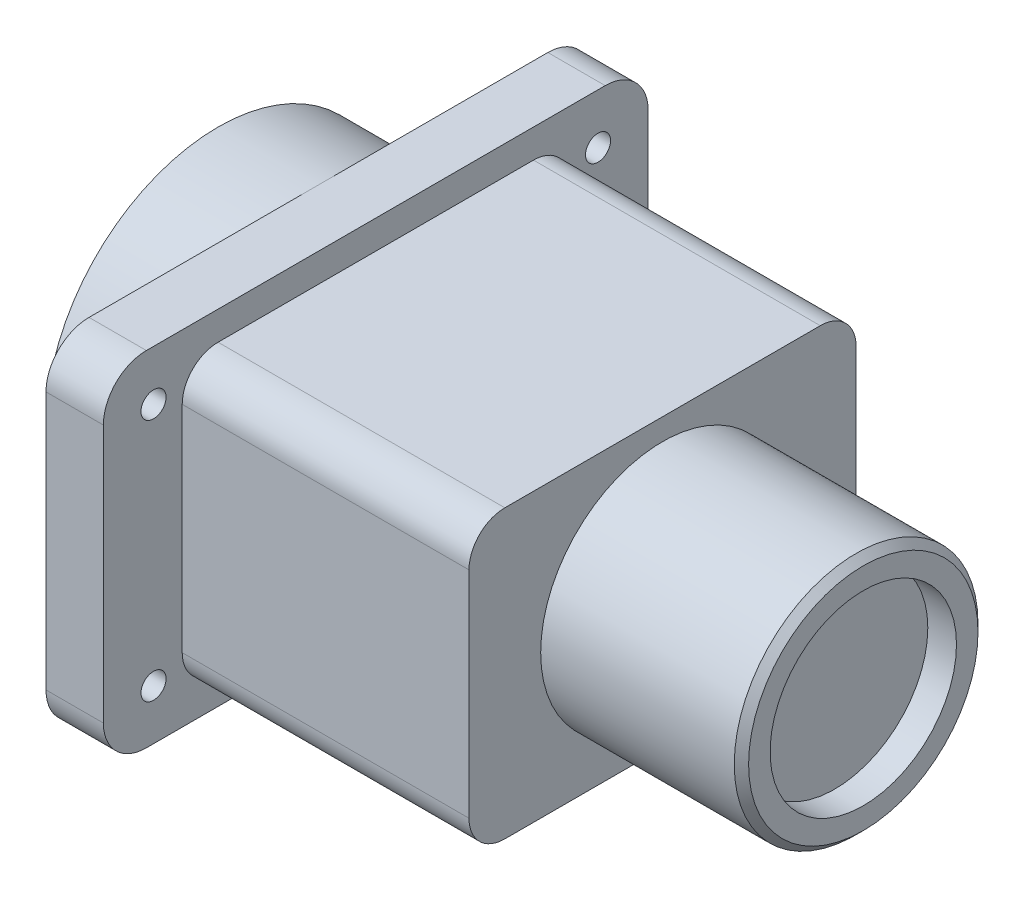
SolidWorks part; units mm, degrees
material "Alliage 6061"
ref_plane "Plan de face" through (0, 0, 0) normal (0, 0, 1) x (1, 0, 0)
ref_plane "Plan de dessus" through (0, 0, 0) normal (0, 1, 0) x (1, 0, 0)
ref_plane "Plan de droite" through (0, 0, 0) normal (1, 0, 0) x (0, 0, -1)
sketch "Esquisse1" plane through (0, 0, 0) normal (1, 0, 0) x (0, 0, -1)
  circle A0 centre (0, 0) radius 24
  dimension "D1" = 48
extrude "Boss.-Extru.1" add sketch "Esquisse1" along normal blind 14
sketch "Esquisse2" plane through (14, 0, 0) normal (1, 0, 0) x (0, 0, -1)
  line L1 (-32, -24) -> (32, -24)
  line L2 (-38, -18) -> (-38, 18)
  line L3 (-32, 24) -> (32, 24)
  line L4 (38, -18) -> (38, 18)
  line L5 (-38, -24) -> (38, 24) construction
  line L6 (-38, 24) -> (38, -24) construction
  arc A0 (-32, -24) -> (-38, -18) centre (-32, -18) cw
  arc A1 (32, -24) -> (38, -18) centre (32, -18) ccw
  arc A2 (-38, 18) -> (-32, 24) centre (-32, 18) cw
  arc A3 (32, 24) -> (38, 18) centre (32, 18) cw
  point P0 (0, 0)
  dimension "D3" = 6
  dimension "D4" = 6
  dimension "D5" = 6
  dimension "D6" = 6
  dimension "D1" = 76
  dimension "D2" = 48
extrude "Boss.-Extru.2" add sketch "Esquisse2" along normal blind 8
sketch "Esquisse3" plane through (22, 0, 0) normal (1, 0, 0) x (0, 0, -1)
  line L0 (-31, 0) -> (31, 0) construction
  line L1 (0, -17) -> (0, 17) construction
  circle A0 centre (31, 17) radius 1.75
  circle A1 centre (-31, 17) radius 1.75
  circle A2 centre (-31, -17) radius 1.75
  circle A3 centre (31, -17) radius 1.75
  dimension "D3" = 3.5
  dimension "D1" = 62
  dimension "D2" = 34
extrude "Enlèv. mat.-Extru.1" cut sketch "Esquisse3" against normal blind 8
sketch "Esquisse4" plane through (22, 0, 0) normal (1, 0, 0) x (0, 0, -1)
  line L1 (-22, -20) -> (22, -20)
  line L2 (-27, -15) -> (-27, 15)
  line L3 (-22, 20) -> (22, 20)
  line L4 (27, -15) -> (27, 15)
  line L5 (-27, -20) -> (27, 20) construction
  line L6 (-27, 20) -> (27, -20) construction
  arc A0 (-22, -20) -> (-27, -15) centre (-22, -15) cw
  arc A1 (22, -20) -> (27, -15) centre (22, -15) ccw
  arc A2 (-27, 15) -> (-22, 20) centre (-22, 15) cw
  arc A3 (22, 20) -> (27, 15) centre (22, 15) cw
  point P0 (0, 0)
  dimension "D3" = 5
  dimension "D4" = 5
  dimension "D5" = 5
  dimension "D6" = 5
  dimension "D1" = 54
  dimension "D2" = 40
extrude "Boss.-Extru.3" add sketch "Esquisse4" along normal blind 40
sketch "Esquisse5" plane through (62, 0, 0) normal (1, 0, 0) x (0, 0, -1)
  circle A0 centre (0, 0) radius 17
  dimension "D1" = 34
extrude "Boss.-Extru.4" add sketch "Esquisse5" along normal blind 28
sketch "Esquisse6" plane through (90, 0, 0) normal (1, 0, 0) x (0, 0, -1)
  circle A0 centre (0, 0) radius 13
  dimension "D1" = 26
extrude "Enlèv. mat.-Extru.2" cut sketch "Esquisse6" against normal blind 4
chamfer "Chanfrein1" distance 1 angle 45 1 edges at (90, 0, -17)
ref_axis "Axis_J5" through (14, 0, 0) along (-1, 0, 0)
